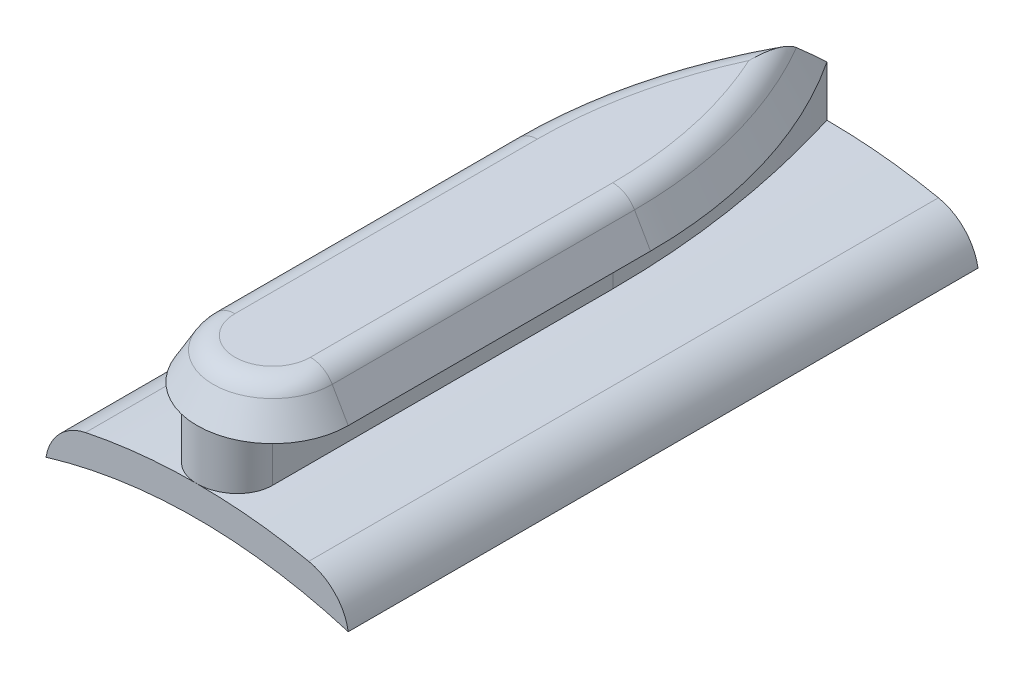
SolidWorks part; units mm, degrees
material "PLA"
ref_plane "Front Plane" through (0, 0, 0) normal (0, 0, 1) x (1, 0, 0)
ref_plane "Top Plane" through (0, 0, 0) normal (0, 1, 0) x (1, 0, 0)
ref_plane "Right Plane" through (0, 0, 0) normal (1, 0, 0) x (0, 0, -1)
sketch "Sketch1" plane through (0, 0, 0) normal (0, 0, 1) x (1, 0, 0)
  line L0 (0, 0.4773) -> (0, 0.8662) construction
  arc A0 (12, -1.7728) -> (-12, -1.7728) centre (0, -41.5) ccw
  arc A1 (8.8602, 1.4966) -> (-8.8602, 1.4966) centre (0, -41.5) ccw
  arc A2 (8.8602, 1.4966) -> (12, -1.7728) centre (8.0529, -2.4211) cw
  arc A3 (-12, -1.7728) -> (-8.8602, 1.4966) centre (-8.0529, -2.4211) cw
  dimension "D1" = 2.4
  dimension "D2" = 83
  dimension "D4" = 4
  dimension "D3" = 24
extrude "Boss-Extrude1" add sketch "Sketch1" along normal blind 50
ref_plane "Plane1" through (0, 2.4, 0) normal (0, 1, 0) x (1, 0, 0)
sketch "Sketch2" plane through (0, 2.4, 0) normal (0, 1, 0) x (1, 0, 0)
  line L0 (-3, -20) -> (-3, -47)
  line L1 (3, -47) -> (3, -20)
  line L2 (0, -1.7439) -> (0, -17.5068) construction
  line L3 (-8.8602, -50) -> (8.8602, -50) construction
  line L4 (8.8602, 0) -> (-8.8602, 0) construction
  arc A0 (-3, -47) -> (3, -47) centre (0, -47) ccw
  arc A1 (3, -20) -> (0, 0) centre (-65.1667, -20) ccw
  arc A2 (-3, -20) -> (0, 0) centre (65.1667, -20) cw
  dimension "D1" = 6
  dimension "D2" = 20
extrude "Boss-Extrude2" add sketch "Sketch2" along normal blind 4 and the other way up to surface other way up to face at (0, 1.9483, 25)
sketch "Sketch3" plane through (0, 6.4, 0) normal (0, 1, 0) x (1, 0, 0)
  line L0 (0, 14.8835) -> (0, -27.446) construction
  line L1 (-6, -20) -> (-6, -44)
  line L2 (6, -44) -> (6, -20)
  arc A0 (-6, -44) -> (6, -44) centre (0, -44) ccw
  arc A1 (6, -20) -> (0, 0) centre (-30.3333, -20) ccw
  arc A2 (-6, -20) -> (0, 0) centre (30.3333, -20) cw
  arc A4 (-3, -47) -> (3, -47) centre (0, -47) ccw construction
  dimension "D2" = 20
  dimension "D1" = 12
extrude "Boss-Extrude3" add sketch "Sketch3" along normal blind 3.2 draft 30
fillet "Fillet1" radius 2 5 edges at (-3.0982, 9.6, 11.5383) (-4.1525, 9.6, 32) (3.0982, 9.6, 11.5383) (4.1525, 9.6, 32) (0, 9.6, 48.1525)
sketch "Sketch4" plane through (0, 0, 0) normal (0, 1, 0) x (1, 0, 0)
  line L0 (-4, -50) -> (-4, 0) construction
  line L1 (12, 0) -> (-12, 0) construction
  line L2 (-12, -50) -> (12, -50) construction
  text T0 "← UP ←" font "Century Gothic" height 8
  dimension "D1" = 4
extrude "Cut-Extrude1" cut sketch "Sketch4" along normal blind 0.2 and the other way through all
